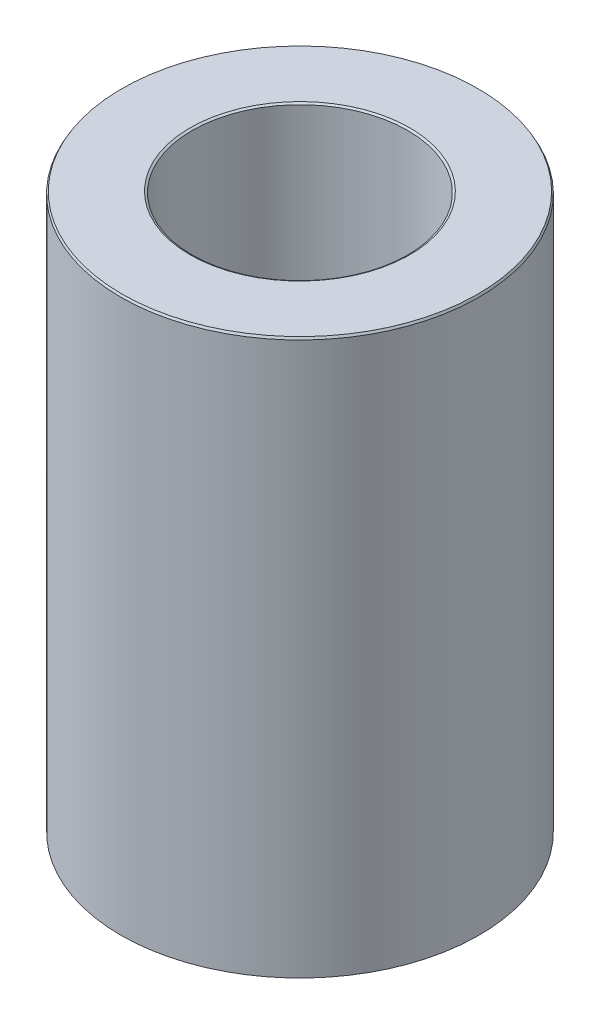
SolidWorks part; units mm, degrees
ref_plane "Front Plane" through (0, 0, 0) normal (0, 0, 1) x (1, 0, 0)
ref_plane "Top Plane" through (0, 0, 0) normal (0, 1, 0) x (1, 0, 0)
ref_plane "Right Plane" through (0, 0, 0) normal (1, 0, 0) x (0, 0, -1)
sketch "Sketch1" plane through (0, 0, 0) normal (0, 1, 0) x (1, 0, 0)
  circle A0 centre (0, 0) radius 25
  dimension "SLEEVE_OD" = 50
extrude "Boss-Extrude1" add sketch "Sketch1" along normal blind 77.5546
sketch "Sketch2" plane through (0, 0, 0) normal (0, 1, 0) x (1, 0, 0)
  circle A0 centre (0, 0) radius 15.0436
  dimension "BORE_D" = 30.0872
extrude "Cut-Extrude1" cut sketch "Sketch2" along normal through all
chamfer "Chamfer1" distance 0.2937 angle 30 4 edges at (0, 77.5546, 15.0436) (0, 0, 15.0436) (0, 0, 25) (0, 77.5546, 25) first distance on face at (0, 77.5546, 15.0436) first distance on face at (0, 0, 15.0436) first distance on face at (0, 77.5546, 25)
